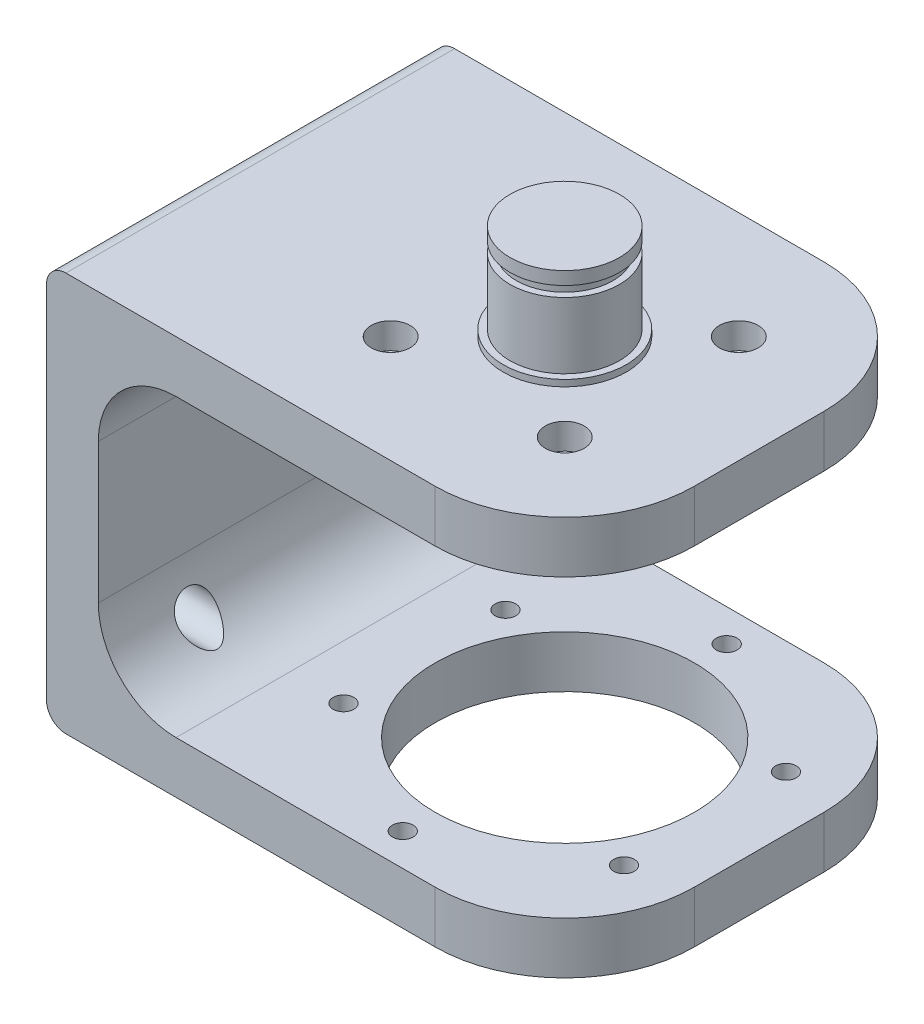
SolidWorks part; units mm, degrees
ref_plane "Front Plane" through (0, 0, 0) normal (0, 0, 1) x (1, 0, 0)
ref_plane "Top Plane" through (0, 0, 0) normal (0, 1, 0) x (1, 0, 0)
ref_plane "Right Plane" through (0, 0, 0) normal (1, 0, 0) x (0, 0, -1)
sketch "草图1" plane through (0, 0, 0) normal (0, 1, 0) x (1, 0, 0)
  line L1 (40, -30) -> (-40, -30)
  line L2 (40, -30) -> (40, 30)
  line L3 (40, 30) -> (-40, 30)
  line L4 (-40, -30) -> (-40, 30)
  line L5 (40, -30) -> (-40, 30) construction
  line L6 (40, 30) -> (-40, -30) construction
  point P0 (0, 0)
  dimension "D1" = 60
  dimension "D2" = 80
extrude "凸台-拉伸1" add sketch "草图1" along normal blind 8
sketch "草图2" plane through (0, 8, 0) normal (0, 1, 0) x (1, 0, 0)
  line L1 (-32, -30) -> (-40, -30)
  line L2 (-32, -30) -> (-32, 30)
  line L3 (-32, 30) -> (-40, 30)
  line L4 (-40, -30) -> (-40, 30)
  line L5 (-32, -30) -> (-40, 30) construction
  line L6 (-32, 30) -> (-40, -30) construction
  point P0 (-36, 0)
  dimension "D1" = 8
extrude "凸台-拉伸2" add sketch "草图2" along normal blind 53.6
sketch "草图5" plane through (-32, 0, 0) normal (1, 0, 0) x (0, 0, -1)
  line L0 (-30, 61.6) -> (-30, 8) construction
  line L1 (30, 53.6) -> (-30, 53.6)
  line L2 (30, 53.6) -> (30, 61.6)
  line L3 (30, 61.6) -> (-30, 61.6)
  line L4 (-30, 53.6) -> (-30, 61.6)
  line L5 (30, 53.6) -> (-30, 61.6) construction
  line L6 (30, 61.6) -> (-30, 53.6) construction
  line L7 (30, 61.6) -> (30, 8) construction
  line L9 (-30, 61.6) -> (30, 61.6) construction
  point P0 (0, 57.6)
  dimension "D1" = 8
extrude "凸台-拉伸3" add sketch "草图5" along normal through all
sketch "草图4" plane through (0, 8, 0) normal (0, 1, 0) x (1, 0, 0)
  line L2 (40, -30) -> (40, 30) construction
  line L3 (40, 30) -> (-32, 30) construction
  circle A0 centre (10, 0) radius 25 construction
  circle A1 centre (10, 25) radius 1.6
  circle A2 centre (-11.6506, 12.5) radius 1.6
  circle A3 centre (-11.6506, -12.5) radius 1.6
  circle A4 centre (10, -25) radius 1.6
  circle A5 centre (10, 0) radius 20
  circle A6 centre (31.6506, -12.5) radius 1.6
  circle A7 centre (31.6506, 12.5) radius 1.6
  point P17 (10, 0)
  dimension "D3" = 50
  dimension "D4" = 3.2
  dimension "D6" = 40
  dimension "D1" = 30
  dimension "D2" = 30
  dimension "D5" = 6
extrude "切除-拉伸1" cut sketch "草图4" against normal through all contours A5 | A2 | A1 | A4 | A3 | A7 | A6
sketch "草图7" plane through (0, 61.6, 0) normal (0, 1, 0) x (1, 0, 0)
  line L1 (40, 30) -> (-40, 30) construction
  line L2 (40, 30) -> (40, -30) construction
  line L3 (10, 0) -> (-3.435, 13.435) construction
  line L4 (10, 0) -> (10, 19) construction
  circle A0 centre (10, 0) radius 19 construction
  circle A5 centre (-3.435, 13.435) radius 1.6
  circle A6 centre (23.435, 13.435) radius 1.6
  circle A7 centre (23.435, -13.435) radius 1.6
  circle A8 centre (-3.435, -13.435) radius 1.6
  point P18 (10, 0)
  point P20 (10, 0)
  dimension "D1" = 38
  dimension "D4" = 45
  dimension "D5" = 3.2
  dimension "D2" = 30
  dimension "D3" = 30
  dimension "D6" = 4
extrude "切除-拉伸3" cut sketch "草图7" against normal up to next
fillet "圆角3" radius 20 4 edges at (40, 4, 30) (40, 4, -30) (40, 57.6, -30) (40, 57.6, 30)
fillet "圆角4" radius 12 2 edges at (-32, 8, 0) (-32, 53.6, 0)
fillet "圆角5" radius 3 2 edges at (-40, 0, 0) (-40, 61.6, 0)
sketch "草图6" plane through (-40, 0, 0) normal (-1, 0, 0) x (0, 0, 1)
  line L0 (-30, 61.6) -> (30, 61.6) construction
  line L1 (17, 13) -> (-17, 13) construction
  line L2 (17, 13) -> (17, 48.6) construction
  line L3 (17, 48.6) -> (-17, 48.6) construction
  line L4 (-17, 13) -> (-17, 48.6) construction
  line L5 (17, 13) -> (-17, 48.6) construction
  line L6 (17, 48.6) -> (-17, 13) construction
  line L7 (30, 0) -> (-30, 0) construction
  line L8 (30, 58.6) -> (30, 3) construction
  line L9 (-30, 58.6) -> (-30, 3) construction
  line L10 (-17, 30.8) -> (17, 30.8) construction
  line L11 (0, 13) -> (0, 48.6) construction
  circle A0 centre (-17, 48.6) radius 1.6
  circle A1 centre (17, 48.6) radius 1.6
  circle A2 centre (17, 13) radius 1.6
  circle A3 centre (-17, 13) radius 1.6
  point P0 (0, 30.8)
  dimension "D5" = 3.2
  dimension "D1" = 13
  dimension "D2" = 13
  dimension "D3" = 13
  dimension "D4" = 13
extrude "切除-拉伸2" cut sketch "草图6" against normal through all
sketch "草图8" plane through (0, 61.6, 0) normal (0, 1, 0) x (1, 0, 0)
  circle A0 centre (10, 0) radius 8.45
  dimension "D1" = 16.9
extrude "凸台-拉伸4" add sketch "草图8" along normal blind 14.8
ref_plane "基准面1" through (0, 74.4, 0) normal (0, 1, 0) x (1, 0, 0)
sketch "草图10" plane through (0, 74.4, 0) normal (0, 1, 0) x (1, 0, 0)
  circle A0 centre (10, 0) radius 8.45
  circle A1 centre (10, 0) radius 7.45
  dimension "D1" = 14.9
extrude "切除-拉伸4" cut sketch "草图10" against normal blind 1.6
ref_plane "基准面2" through (-36, 0, 0) normal (-1, 0, 0) x (0, 0, 1)
sketch "草图12" plane through (-36, 0, 0) normal (-1, 0, 0) x (0, 0, 1)
  line L0 (-30, 30.8) -> (30, 30.8) construction
  line L1 (-30, 58.6) -> (-30, 3) construction
  line L2 (30, 58.6) -> (30, 3) construction
  line L3 (0, 61.6) -> (0, 3) construction
  line L4 (8.45, 61.6) -> (-8.45, 61.6) construction
  line L5 (-30, 3) -> (30, 3) construction
  circle A0 centre (-17, 48.6) radius 3
  circle A1 centre (17, 48.6) radius 3
  circle A2 centre (17, 13) radius 3
  circle A3 centre (-17, 13) radius 3
  dimension "D1" = 6
extrude "切除-拉伸5" cut sketch "草图12" against normal up to next
sketch "草图14" plane through (0, 61.6, 0) normal (0, 1, 0) x (1, 0, 0)
  circle A0 centre (-3.435, 13.435) radius 3
  circle A1 centre (23.435, 13.435) radius 3
  circle A2 centre (23.435, -13.435) radius 3
  circle A3 centre (-3.435, -13.435) radius 3
  point P3 (0, 0)
  point P4 (10.9108, -1.9865)
  point P5 (10, 0)
  point P12 (10, 0)
  dimension "D1" = 6
  dimension "D2" = 4
extrude "切除-拉伸6" cut sketch "草图14" against normal blind 4
sketch "草图15" plane through (0, 0, 0) normal (0, -1, 0) x (1, 0, 0)
  circle A0 centre (-11.6506, 12.5) radius 3
  circle A1 centre (10, 25) radius 3
  circle A2 centre (31.6506, 12.5) radius 3
  circle A3 centre (31.6506, -12.5) radius 3
  circle A4 centre (10, -25) radius 3
  circle A5 centre (-11.6506, -12.5) radius 3
  point P4 (10, 0)
  point P15 (10, 0)
  dimension "D1" = 6
  dimension "D2" = 6
extrude "切除-拉伸7" cut sketch "草图15" against normal blind 4
sketch "草图16" plane through (0, 61.6, 0) normal (0, 1, 0) x (1, 0, 0)
  circle A0 centre (10, 0) radius 9.5
  dimension "D1" = 19
extrude "凸台-拉伸5" add sketch "草图16" along normal blind 1
